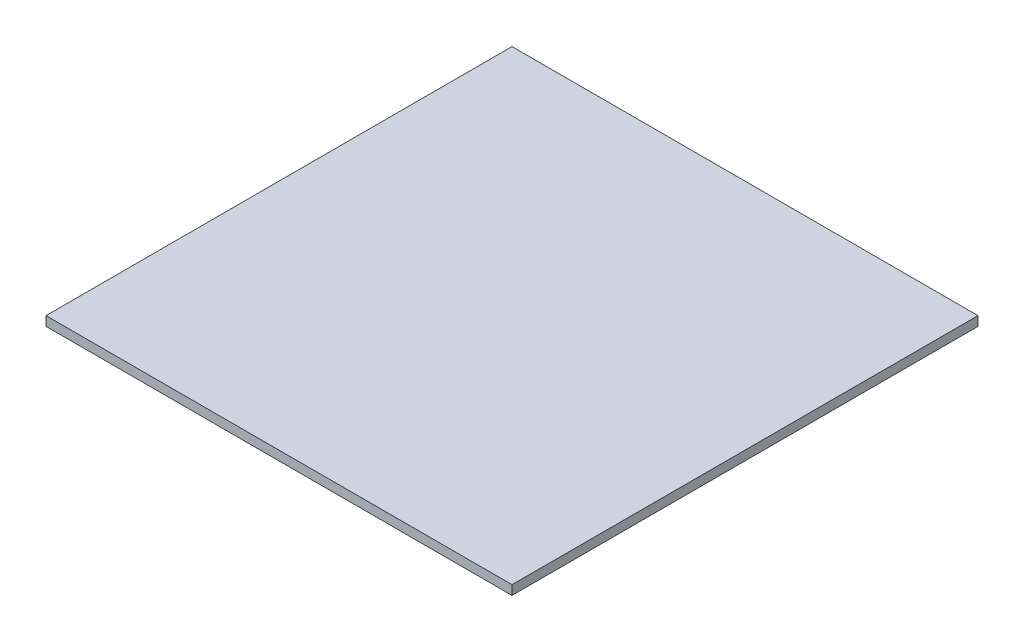
SolidWorks part; units mm, degrees
material "AISI 1045 Steel, cold drawn"
ref_plane "Front Plane" through (0, 0, 0) normal (0, 0, 1) x (1, 0, 0)
ref_plane "Top Plane" through (0, 0, 0) normal (0, 1, 0) x (1, 0, 0)
ref_plane "Right Plane" through (0, 0, 0) normal (1, 0, 0) x (0, 0, -1)
sketch "Sketch1" plane through (0, 0, 0) normal (0, 1, 0) x (1, 0, 0)
  line L1 (250, -250) -> (-250, -250)
  line L2 (250, -250) -> (250, 250)
  line L3 (250, 250) -> (-250, 250)
  line L4 (-250, -250) -> (-250, 250)
  line L5 (250, -250) -> (-250, 250) construction
  line L6 (250, 250) -> (-250, -250) construction
  point P0 (0, 0)
  dimension "D1" = 500
extrude "Boss-Extrude1" add sketch "Sketch1" along normal blind 10
